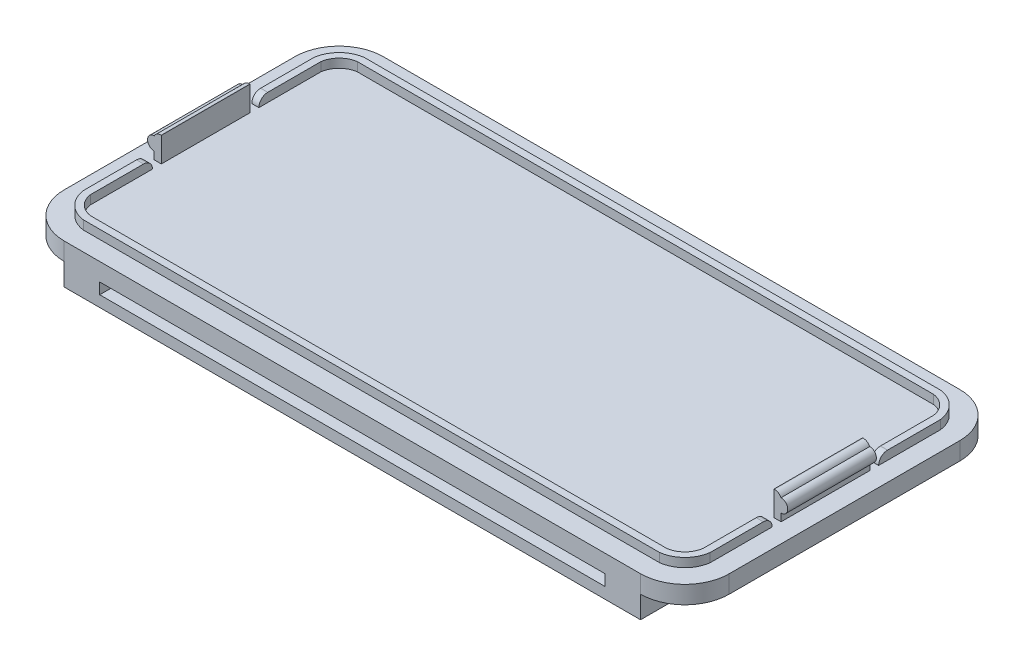
SolidWorks part; units mm, degrees
ref_plane "前视基准面" through (0, 0, 0) normal (0, 0, 1) x (1, 0, 0)
ref_plane "上视基准面" through (0, 0, 0) normal (0, 1, 0) x (1, 0, 0)
ref_plane "右视基准面" through (0, 0, 0) normal (1, 0, 0) x (0, 0, -1)
sketch "zero" plane through (0, 0, 0) normal (0, 1, 0) x (1, 0, 0)
  line L1 (-29.5, 15) -> (29.5, 15)
  line L2 (-32.5, 12) -> (-32.5, -12)
  line L3 (-29.5, -15) -> (29.5, -15)
  line L4 (32.5, 12) -> (32.5, -12)
  line L5 (-32.5, 15) -> (32.5, -15) construction
  line L6 (-32.5, -15) -> (32.5, 15) construction
  line L7 (-25.7, -15) -> (-14.5, -15)
  line L8 (-25.7, -15) -> (-25.7, -9.6569)
  line L9 (-25.7, -9.6569) -> (-14.5, -9.6569)
  line L10 (-14.5, -15) -> (-14.5, -9.6569)
  line L11 (5.2, -15) -> (12.7, -15)
  line L12 (5.2, -15) -> (5.2, -11)
  line L13 (5.2, -11) -> (12.7, -11)
  line L14 (12.7, -15) -> (12.7, -11)
  line L15 (17.8, -15) -> (25.3, -15)
  line L16 (17.8, -15) -> (17.8, -11)
  line L17 (17.8, -11) -> (25.3, -11)
  line L18 (25.3, -15) -> (25.3, -11)
  line L19 (-32.5, 7.7) -> (-19.5, 7.7)
  line L20 (-32.5, 7.7) -> (-32.5, -4.3)
  line L21 (-32.5, -4.3) -> (-19.5, -4.3)
  line L22 (-19.5, 7.7) -> (-19.5, -4.3)
  line L23 (-25.5, 14) -> (25.5, 14)
  line L24 (-25.5, 14) -> (-25.5, 8.8)
  line L25 (-25.5, 8.8) -> (25.5, 8.8)
  line L26 (25.5, 14) -> (25.5, 8.8)
  line L27 (-19.5, 7.2329) -> (-35.5, 7.2329)
  line L28 (-19.5, 7.2329) -> (-19.5, -3.7671)
  line L29 (-19.5, -3.7671) -> (-35.5, -3.7671)
  line L30 (-35.5, 7.2329) -> (-35.5, -3.7671)
  arc A0 (29.5, -15) -> (32.5, -12) centre (29.5, -12) ccw
  arc A1 (29.5, 15) -> (32.5, 12) centre (29.5, 12) cw
  arc A2 (-32.5, -12) -> (-29.5, -15) centre (-29.5, -12) ccw
  arc A3 (-29.5, 15) -> (-32.5, 12) centre (-29.5, 12) ccw
  circle A4 centre (-29, 11.4) radius 3
  circle A5 centre (-29, -11.5) radius 3
  circle A6 centre (29, 11.4) radius 3
  circle A7 centre (29, -11.5) radius 3
  circle A8 centre (-29, 11.4) radius 1.375
  circle A9 centre (-29, -11.5) radius 1.375
  circle A10 centre (29, -11.5) radius 1.375
  circle A11 centre (29, 11.4) radius 1.375
  point P0 (0, 0)
  dimension "D3" = 3
  dimension "D4" = 6
  dimension "D9" = 2.75
  dimension "D1" = 65
  dimension "D2" = 30
  dimension "D5" = 3.6
  dimension "D6" = 3.5
  dimension "D7" = 3.5
  dimension "D8" = 3.5
  dimension "D10" = 12
  dimension "D11" = 7.3
  dimension "D12" = 13
  dimension "D13" = 11.2
  dimension "D14" = 6.8
  dimension "D15" = 19.7
  dimension "D16" = 7.5
  dimension "D17" = 7.5
  dimension "D18" = 5.1
  dimension "D19" = 4
  dimension "D20" = 5.2
  dimension "D21" = 7
  dimension "D22" = 7
  dimension "D23" = 1
  dimension "D24" = 11
  dimension "D25" = 16
sketch "sugar" plane through (0, 0, 0) normal (0, 1, 0) x (1, 0, 0)
  line L1 (-29.5, 15) -> (29.5, 15)
  line L2 (-32.5, 12) -> (-32.5, -12)
  line L3 (-29.5, -15) -> (29.5, -15)
  line L4 (32.5, 12) -> (32.5, -12)
  line L5 (-32.5, 15) -> (32.5, -15) construction
  line L6 (-32.5, -15) -> (32.5, 15) construction
  line L7 (23.5, -11.5) -> (19.5, -11.5)
  line L8 (23.5, -11.5) -> (23.5, -13.9082)
  line L9 (23.5, -13.9082) -> (19.5, -13.9082)
  line L10 (19.5, -11.5) -> (19.5, -13.9082)
  line L11 (16, -11.0071) -> (8.5, -11.0071)
  line L12 (16, -11.0071) -> (16, -15)
  line L13 (16, -15) -> (8.5, -15)
  line L14 (8.5, -11.0071) -> (8.5, -15)
  line L15 (20.5, -13.9082) -> (22.5, -13.9082)
  line L16 (20.5, -13.9082) -> (20.5, -14.8173)
  line L17 (20.5, -14.8173) -> (22.5, -14.8173)
  line L18 (22.5, -13.9082) -> (22.5, -14.8173)
  arc A0 (29.5, 15) -> (32.5, 12) centre (29.5, 12) cw
  arc A1 (29.5, -15) -> (32.5, -12) centre (29.5, -12) ccw
  arc A2 (-32.5, -12) -> (-29.5, -15) centre (-29.5, -12) ccw
  arc A3 (-29.5, 15) -> (-32.5, 12) centre (-29.5, 12) ccw
  circle A4 centre (-29, 11.4) radius 3
  circle A5 centre (-29, 11.4) radius 1.375
  circle A6 centre (-29, -11.5) radius 3
  circle A7 centre (-29, -11.5) radius 1.375
  circle A8 centre (29, 11.4) radius 3
  circle A9 centre (29, 11.4) radius 1.375
  circle A10 centre (29, -11.5) radius 3
  circle A11 centre (29, -11.5) radius 1.375
  dimension "D3" = 3
  dimension "D1" = 65
  dimension "D2" = 30
  dimension "D4" = 9
  dimension "D5" = 4
  dimension "D6" = 3.5
  dimension "D7" = 7.5
  dimension "D8" = 2
  dimension "D9" = 1
sketch "case" plane through (0, 0, 0) normal (0, 1, 0) x (1, 0, 0)
  line L1 (-34.0422, 18) -> (30.9578, 18)
  line L2 (-39.0422, 13) -> (-39.0422, -13)
  line L3 (-34.0422, -18) -> (30.9578, -18)
  line L4 (35.9578, 13) -> (35.9578, -13)
  line L5 (-39.0422, 18) -> (35.9578, -18) construction
  line L6 (-39.0422, -18) -> (35.9578, 18) construction
  arc A0 (-39.0422, -13) -> (-34.0422, -18) centre (-34.0422, -13) ccw
  arc A1 (30.9578, -18) -> (35.9578, -13) centre (30.9578, -13) ccw
  arc A2 (30.9578, 18) -> (35.9578, 13) centre (30.9578, 13) cw
  arc A3 (-34.0422, 18) -> (-39.0422, 13) centre (-34.0422, 13) ccw
  point P0 (-1.5422, 0)
  point P3 (-1.5422, 0)
  dimension "D3" = 5
  dimension "D1" = 75
  dimension "D2" = 36
extrude "凸台-拉伸2" add sketch "case" along normal blind 2
sketch "草图2" plane through (0, 0, 0) normal (0, 1, 0) x (1, 0, 0)
  line L4 (-34.0422, -15.05) -> (30.9578, -15.05)
  line L5 (33.0078, -13) -> (33.0078, 13)
  line L6 (30.9578, 15.05) -> (-34.0422, 15.05)
  line L7 (-36.0922, 13) -> (-36.0922, -13)
  line L12 (33.8078, -13) -> (33.8078, 13)
  line L13 (30.9578, 15.85) -> (-34.0422, 15.85)
  line L14 (-36.8922, 13) -> (-36.8922, -13)
  line L15 (-34.0422, -15.85) -> (30.9578, -15.85)
  arc A4 (30.9578, -15.05) -> (33.0078, -13) centre (30.6303, -12.6725) ccw
  arc A5 (33.0078, 13) -> (30.9578, 15.05) centre (30.6303, 12.6725) ccw
  arc A6 (-34.0422, 15.05) -> (-36.0922, 13) centre (-33.7147, 12.6725) ccw
  arc A7 (-36.0922, -13) -> (-34.0422, -15.05) centre (-33.7147, -12.6725) ccw
  arc A12 (30.9578, -15.85) -> (33.8078, -13) centre (30.535, -12.5772) ccw
  arc A13 (33.8078, 13) -> (30.9578, 15.85) centre (30.535, 12.5772) ccw
  arc A14 (-34.0422, 15.85) -> (-36.8922, 13) centre (-33.6194, 12.5772) ccw
  arc A15 (-36.8922, -13) -> (-34.0422, -15.85) centre (-33.6194, -12.5772) ccw
ref_plane "基准面1" through (0, 2, 0) normal (0, 1, 0) x (1, 0, 0)
sketch "草图3" plane through (0, 2, 0) normal (0, 1, 0) x (1, 0, 0)
  line L4 (-34.0422, -15.05) -> (30.9578, -15.05)
  line L5 (33.0078, -13) -> (33.0078, 13)
  line L6 (30.9578, 15.05) -> (-34.0422, 15.05)
  line L7 (-36.0922, 13) -> (-36.0922, -13)
  line L8 (-34.0422, -15.05) -> (30.9578, -15.05)
  line L9 (33.0078, -13) -> (33.0078, 13)
  line L10 (30.9578, 15.05) -> (-34.0422, 15.05)
  line L11 (-36.0922, 13) -> (-36.0922, -13)
  line L12 (-36.8922, 13) -> (-36.8922, -13)
  line L13 (-34.0422, -15.85) -> (30.9578, -15.85)
  line L14 (33.8078, -13) -> (33.8078, 13)
  line L15 (30.9578, 15.85) -> (-34.0422, 15.85)
  line L16 (-36.8922, 13) -> (-36.8922, -13)
  line L17 (-34.0422, -15.85) -> (30.9578, -15.85)
  line L18 (33.8078, -13) -> (33.8078, 13)
  line L19 (30.9578, 15.85) -> (-34.0422, 15.85)
  arc A4 (30.9578, -15.05) -> (33.0078, -13) centre (30.6303, -12.6725) ccw
  arc A5 (33.0078, 13) -> (30.9578, 15.05) centre (30.6303, 12.6725) ccw
  arc A6 (-34.0422, 15.05) -> (-36.0922, 13) centre (-33.7147, 12.6725) ccw
  arc A7 (-36.0922, -13) -> (-34.0422, -15.05) centre (-33.7147, -12.6725) ccw
  arc A8 (30.9578, -15.05) -> (33.0078, -13) centre (30.6303, -12.6725) ccw
  arc A9 (33.0078, 13) -> (30.9578, 15.05) centre (30.6303, 12.6725) ccw
  arc A10 (-34.0422, 15.05) -> (-36.0922, 13) centre (-33.7147, 12.6725) ccw
  arc A11 (-36.0922, -13) -> (-34.0422, -15.05) centre (-33.7147, -12.6725) ccw
  arc A12 (-36.8922, -13) -> (-34.0422, -15.85) centre (-33.6194, -12.5772) ccw
  arc A13 (30.9578, -15.85) -> (33.8078, -13) centre (30.535, -12.5772) ccw
  arc A14 (33.8078, 13) -> (30.9578, 15.85) centre (30.535, 12.5772) ccw
  arc A15 (-34.0422, 15.85) -> (-36.8922, 13) centre (-33.6194, 12.5772) ccw
  arc A16 (-36.8922, -13) -> (-34.0422, -15.85) centre (-33.6194, -12.5772) ccw
  arc A17 (30.9578, -15.85) -> (33.8078, -13) centre (30.535, -12.5772) ccw
  arc A18 (33.8078, 13) -> (30.9578, 15.85) centre (30.535, 12.5772) ccw
  arc A19 (-34.0422, 15.85) -> (-36.8922, 13) centre (-33.6194, 12.5772) ccw
  dimension "D1" = 0
  dimension "D2" = 0
extrude "凸台-拉伸4" add sketch "草图3" along normal blind 1
ref_plane "基准面3" through (33.8078, 0, 0) normal (1, 0, 0) x (0, 0, -1)
sketch "草图7" plane through (0, 2, 0) normal (0, 1, 0) x (1, 0, 0)
  line L0 (-36.8922, 13) -> (-36.8922, -13) construction
  line L1 (-36.8922, 5) -> (-36.0922, 5)
  line L2 (-36.8922, 5) -> (-36.8922, -5)
  line L3 (-36.8922, -5) -> (-36.0922, -5)
  line L4 (-36.0922, 5) -> (-36.0922, -5)
  line L5 (-36.0922, 13) -> (-36.0922, -13) construction
  point P10 (-36.0922, 0)
  dimension "D1" = 5
  dimension "D2" = 10
extrude "凸台-拉伸8" add sketch "草图7" along normal blind 2.8
ref_plane "基准面5" through (0, 0, 5) normal (0, 0, 1) x (1, 0, 0)
sketch "草图8" plane through (0, 0, 5) normal (0, 0, 1) x (1, 0, 0)
  line L0 (-34.0422, 2) -> (-39.0422, 2) construction
  line L1 (-36.8922, 4.8) -> (-36.8922, 3) construction
  circle A0 centre (-36.8922, 3.6) radius 0.75
  dimension "D1" = 1.5
  dimension "D2" = 1.6
  dimension "D3" = 0
extrude "凸台-拉伸9" add sketch "草图8" against normal blind 10
fillet "圆角1" radius 0.85 1 edges at (-36.8922, 4.8, 0)
ref_plane "基准面7" through (-36.8922, 0, 0) normal (-1, 0, 0) x (0, 0, 1)
sketch "草图11" plane through (-36.8922, 0, 0) normal (-1, 0, 0) x (0, 0, 1)
  line L0 (-13, 2) -> (13, 2) construction
  line L1 (5, 3) -> (6, 3)
  line L2 (5, 3) -> (5, 2)
  line L3 (5, 2) -> (6, 2)
  line L4 (6, 3) -> (6, 2)
  line L6 (-5, 3) -> (-6, 3)
  line L7 (-5, 3) -> (-5, 2)
  line L8 (-5, 2) -> (-6, 2)
  line L9 (-6, 3) -> (-6, 2)
  dimension "D1" = 1
  dimension "D2" = 1
extrude "切除-拉伸1" cut sketch "草图11" against normal blind 1.2
fillet "圆角2" radius 1 2 edges at (-36.4922, 3, 6) (-36.4922, 3, -6)
ref_plane "基准面8" through (0, 0, 0) normal (0, -1, 0) x (-1, 0, 0)
sketch "草图13" plane through (0, 3, 0) normal (0, 1, 0) x (1, 0, 0)
  line L0 (33.0078, -13) -> (33.0078, 13) construction
  line L1 (33.0078, 5) -> (33.8078, 5)
  line L2 (33.0078, 5) -> (33.0078, -5)
  line L3 (33.0078, -5) -> (33.8078, -5)
  line L4 (33.8078, 5) -> (33.8078, -5)
  line L5 (33.8078, -13) -> (33.8078, 13) construction
  line L7 (35.9578, -13) -> (35.9578, 13) construction
  point P12 (35.9578, 0)
  point P13 (33.8078, 0)
  dimension "D1" = 10
sketch "Sketch3" plane through (0, 0, 0) normal (0, -1, 0) x (1, 0, 0)
  text T0 "<b>PeakPulse</b>" font "Century Gothic" height 10
extrude "Cut-Extrude1" cut sketch "Sketch3" against normal blind 1
extrude "凸台-拉伸10" add sketch "草图13" along normal blind 1.8
sketch "草图14" plane through (0, 0, 5) normal (0, 0, 1) x (1, 0, 0)
  line L0 (33.8078, 2) -> (30.9578, 2) construction
  line L1 (33.8078, 4.8) -> (33.8078, 3) construction
  circle A0 centre (33.8078, 3.6) radius 0.75
  dimension "D2" = 1.5
  dimension "D1" = 1.6
  dimension "D3" = 0
extrude "凸台-拉伸11" add sketch "草图14" against normal blind 10
fillet "圆角3" radius 0.85 1 edges at (33.8078, 4.8, 0)
sketch "草图15" plane through (0, 3, 0) normal (0, 1, 0) x (1, 0, 0)
  line L0 (33.8078, 5) -> (33.8078, 13) construction
  line L1 (33.0078, 5) -> (33.8078, 5)
  line L2 (33.0078, 5) -> (33.0078, 6)
  line L3 (33.0078, 6) -> (33.8078, 6)
  line L4 (33.8078, 5) -> (33.8078, 6)
  line L5 (33.8078, -13) -> (33.8078, -5) construction
  line L6 (33.0078, -5) -> (33.8078, -5)
  line L7 (33.0078, -5) -> (33.0078, -6)
  line L8 (33.0078, -6) -> (33.8078, -6)
  line L9 (33.8078, -5) -> (33.8078, -6)
  dimension "D1" = 1
  dimension "D2" = 1
extrude "切除-拉伸3" cut sketch "草图15" against normal blind 1
fillet "圆角4" radius 1 2 edges at (33.4078, 3, 6) (33.4078, 3, -6)
sketch "Sketch2" plane through (0, 2, 0) normal (0, 1, 0) x (1, 0, 0)
  line L0 (8.6467, -7.2235) -> (-6.9133, -7.2235)
  circle A0 centre (8.6467, -7.2235) radius 1.5
  circle A1 centre (-6.9133, -7.2235) radius 1.5
  circle A2 centre (-6.9133, -7.2235) radius 2.5
  circle A3 centre (8.6467, -7.2235) radius 2.5
sketch "Sketch5" plane through (0, 0, 0) normal (0, -1, 0) x (1, 0, 0)
  line L1 (-34.0422, 18) -> (-30.0422, 18)
  line L2 (-34.0422, 18) -> (-34.0422, 10)
  line L3 (-34.0422, 10) -> (-30.0422, 10)
  line L4 (-30.0422, 18) -> (-30.0422, 10)
  line L5 (26.9578, 18) -> (30.9578, 18)
  line L6 (-34.0422, 18) -> (30.9578, 18) construction
  line L7 (30.9578, 18) -> (30.9578, 10)
  line L8 (26.9578, 10) -> (26.9578, 18)
  line L9 (30.9578, 10) -> (26.9578, 10)
  line L10 (-34.0422, -18) -> (-34.0422, -10)
  line L11 (-34.0422, -10) -> (-30.0422, -10)
  line L12 (-30.0422, -10) -> (-30.0422, -18)
  line L13 (30.9578, -18) -> (-34.0422, -18) construction
  line L14 (-30.0422, -18) -> (-34.0422, -18)
  line L15 (30.9578, -18) -> (30.9578, -10)
  line L16 (30.9578, -10) -> (26.9578, -10)
  line L17 (26.9578, -10) -> (26.9578, -18)
  line L18 (26.9578, -18) -> (30.9578, -18)
  arc A0 (30.9578, -18) -> (35.9578, -13) centre (30.9578, -13) ccw construction
extrude "Boss-Extrude1" add sketch "Sketch5" along normal blind 2.5 contours L2 L1 L4 L3 | L14 L10 L11 L12 | L9 L8 L5 L7 | L18 L15 L16 L17
sketch "Sketch7" plane through (26.9578, 0, 0) normal (-1, 0, 0) x (0, 0, 1)
  line L0 (10, -2.5) -> (10, -1.25)
  line L1 (10, -2.5) -> (10, 0) construction
  line L2 (10, -1.25) -> (18, -1.25)
  line L3 (18, -2.5) -> (18, 0) construction
  line L4 (18, -1.25) -> (18, -2.5)
  line L5 (18, -2.5) -> (10, -2.5) construction
  line L6 (18, -2.5) -> (10, -2.5)
  line L7 (-18, -2.5) -> (-18, -1.25)
  line L8 (-18, -2.5) -> (-18, 0) construction
  line L9 (-18, -1.25) -> (-10, -1.25)
  line L10 (-10, -2.5) -> (-10, 0) construction
  line L11 (-10, -1.25) -> (-10, -2.5)
  line L12 (-10, -2.5) -> (-18, -2.5)
extrude "Boss-Extrude2" add sketch "Sketch7" along normal up to next
